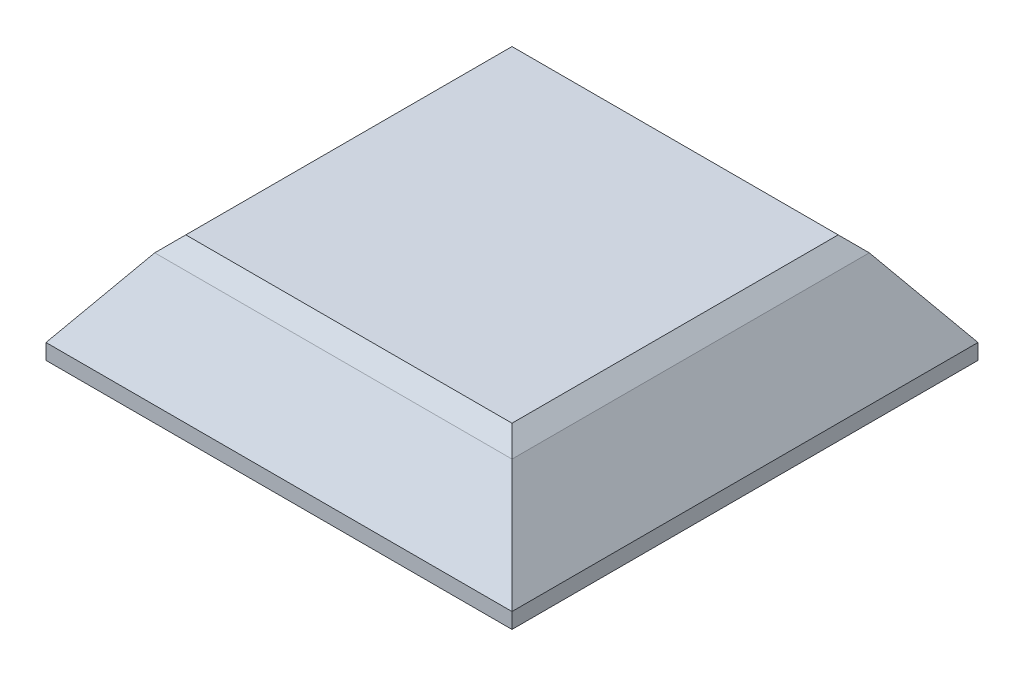
SolidWorks part; units mm, degrees
ref_plane "Front Plane" through (0, 0, 0) normal (0, 0, 1) x (1, 0, 0)
ref_plane "Top Plane" through (0, 0, 0) normal (0, 1, 0) x (1, 0, 0)
ref_plane "Right Plane" through (0, 0, 0) normal (1, 0, 0) x (0, 0, -1)
sketch "Sketch1" plane through (0, 0, 0) normal (0, -1, 0) x (1, 0, 0)
  line L8 (-30.275, -28.5776) -> (-84.275, -28.5776)
  line L9 (-32.275, -30.5776) -> (-82.275, -30.5776)
  line L10 (-32.275, -30.5776) -> (-32.275, -80.5776)
  line L11 (-32.275, -80.5776) -> (-82.275, -80.5776)
  line L12 (-82.275, -30.5776) -> (-82.275, -80.5776)
  line L13 (-84.275, -28.5776) -> (-84.275, -82.5776)
  line L14 (-30.275, -82.5776) -> (-84.275, -82.5776)
  line L15 (-30.275, -28.5776) -> (-30.275, -82.5776)
  line L17 (-45.6393, -46.3786) -> (-70.6393, -46.3786)
  line L18 (-45.6393, -46.3786) -> (-45.6393, -66.3786)
  line L19 (-45.6393, -66.3786) -> (-70.6393, -66.3786)
  line L20 (-70.6393, -46.3786) -> (-70.6393, -66.3786)
  line L26 (-34.275, -32.5776) -> (-80.275, -32.5776)
  line L39 (-80.275, -32.5776) -> (-80.275, -78.5776)
  line L40 (-34.275, -78.5776) -> (-80.275, -78.5776)
  line L41 (-34.275, -32.5776) -> (-34.275, -78.5776)
  line L42 (-27.275, -25.5776) -> (-27.275, -85.5776)
  line L55 (-82.275, -66.3786) -> (-84.275, -66.3786)
  line L56 (-82.275, -66.3786) -> (-82.275, -46.3786)
  line L57 (-82.275, -46.3786) -> (-84.275, -46.3786)
  line L58 (-84.275, -66.3786) -> (-84.275, -46.3786)
  line L59 (-27.275, -85.5776) -> (-87.275, -85.5776)
  line L60 (-87.275, -25.5776) -> (-87.275, -85.5776)
  line L61 (-27.275, -25.5776) -> (-87.275, -25.5776)
  line L62 (-82.275, -46.8786) -> (-84.275, -46.8786)
  line L63 (-82.275, -65.8786) -> (-84.275, -65.8786)
  circle A4 centre (-45.6393, -46.3786) radius 2.5
  circle A5 centre (-70.6393, -46.3786) radius 2.5
  circle A6 centre (-45.6393, -66.3786) radius 2.5
  circle A7 centre (-70.6393, -66.3786) radius 2.5
  circle A12 centre (-34.275, -32.5776) radius 4
  circle A13 centre (-80.275, -32.5776) radius 4
  circle A14 centre (-80.275, -78.5776) radius 4
  circle A15 centre (-34.275, -78.5776) radius 4
  circle A16 centre (-34.275, -32.5776) radius 4.5
  circle A17 centre (-80.275, -32.5776) radius 4.5
  circle A18 centre (-80.275, -78.5776) radius 4.5
  circle A19 centre (-34.275, -78.5776) radius 4.5
  dimension "D4" = 50
  dimension "D2" = 3
  dimension "D5" = 50
  dimension "D7" = 25
  dimension "D8" = 20
  dimension "D3" = 0.5
  dimension "D6" = 2
  dimension "D9" = 0.5
  dimension "D10" = 0.5
  dimension "D13" = 2
extrude "Boss-Extrude1" add sketch "Sketch1" against normal blind 2 contours L42 L59 L60 L61
extrude "Boss-Extrude2" add sketch "Sketch1<18>" against normal blind 2 from offset 12 separate body contours L40 L39 L26 L41 offset against normal yes
sketch "Sketch1<18>" plane through (0, 0, 0) normal (0, -1, 0) x (1, 0, 0) same geometry as "Sketch1"
loft "Loft1" add section face at (-57.275, 2, -55.5776) section face at (-57.275, 12, -55.5776) connector at (-87.275, 2, -85.5776) connector at (-80.275, 12, -78.5776)
chamfer "Chamfer1" distance 2 angle 45 4 edges at (-57.275, 14, -32.5776) (-34.275, 14, -55.5776) (-57.275, 14, -78.5776) (-80.275, 14, -55.5776)
extrude "Cut-Extrude4" cut sketch "Sketch1<19>" against normal blind 8 contours L41 L40 L39 L26
sketch "Sketch1<19>" plane through (0, 0, 0) normal (0, -1, 0) x (1, 0, 0) same geometry as "Sketch1"
chamfer "Chamfer2" distance 5 angle 45 4 edges at (-57.275, 8, -78.5776) (-80.275, 8, -55.5776) (-57.275, 8, -32.5776) (-34.275, 8, -55.5776)
extrude "Cut-Extrude5" cut sketch "Sketch1<21>" against normal blind 5 contours A17 | A16 | A18 | A19
sketch "Sketch1<21>" plane through (0, 0, 0) normal (0, -1, 0) x (1, 0, 0) same geometry as "Sketch1"
fillet "Fillet1" radius 1.5 3 edges at (-83.457, 5, -81.7596) (-83.457, 5, -29.3957) (-31.093, 5, -81.7596)
extrude "Boss-Extrude3" add sketch "Sketch1<22>" along normal blind 15 contours L56 L63 L58 L62 region at (-83.275, 0, -56.3786)
sketch "Sketch1<22>" plane through (0, 0, 0) normal (0, -1, 0) x (1, 0, 0) same geometry as "Sketch1"
fillet "Fillet2" radius 1.5 2 edges at (-82.275, 0, -56.3786) (-84.275, 0, -56.3786)
